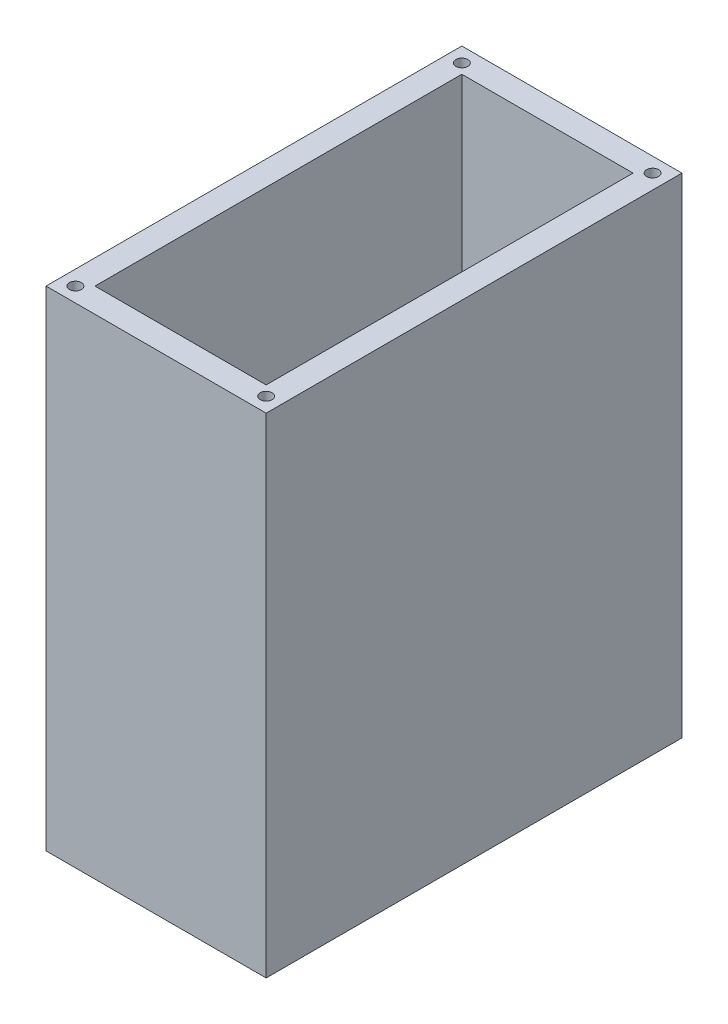
SolidWorks part; units mm, degrees
ref_plane "Front Plane" through (0, 0, 0) normal (0, 0, 1) x (1, 0, 0)
ref_plane "Top Plane" through (0, 0, 0) normal (0, 1, 0) x (1, 0, 0)
ref_plane "Right Plane" through (0, 0, 0) normal (1, 0, 0) x (0, 0, -1)
sketch "Sketch1" plane through (0, 0, 0) normal (0, 1, 0) x (1, 0, 0)
  line L1 (-22.5, 42.5) -> (22.5, 42.5)
  line L2 (-22.5, 42.5) -> (-22.5, -42.5)
  line L3 (-22.5, -42.5) -> (22.5, -42.5)
  line L4 (22.5, 42.5) -> (22.5, -42.5)
  line L5 (-22.5, 42.5) -> (22.5, -42.5) construction
  line L6 (-22.5, -42.5) -> (22.5, 42.5) construction
  point P0 (0, 0)
  dimension "D1" = 45
  dimension "D2" = 85
extrude "Boss-Extrude1" add sketch "Sketch1" along normal blind 100
shell "Shell1" thickness 5 removed face at (0, 100, 0)
sketch "Sketch2" plane through (0, 5, 0) normal (0, 1, 0) x (1, 0, 0)
  line L0 (-13.25, 0) -> (-13.25, -29)
  line L1 (-13.25, -29) -> (-1.25, -29)
  line L2 (-1.25, -29) -> (-1.25, -13.1909)
  line L3 (-16.25, 0) -> (-16.25, -32)
  line L4 (-16.25, -32) -> (1.75, -32)
  line L5 (1.75, -32) -> (1.75, -13.1339)
  line L6 (-13.25, 0) -> (-16.25, 0)
  line L7 (3.4294, 12.7985) -> (4.2058, 15.6963)
  line L8 (-4.2058, 15.6963) -> (-3.4294, 12.7985)
  line L9 (-1.25, -16.2019) -> (-1.25, -13.1909)
  line L10 (-1.25, -29) -> (-1.25, -12.0576) construction
  line L11 (1.75, -32) -> (1.75, -12.0576) construction
  line L12 (1.75, -16.1555) -> (1.75, -13.1339)
  line L13 (-1.25, -16.2019) -> (-1.25, -13.1909)
  line L14 (1.75, -13.1339) -> (1.75, -16.1555)
  line L19 (-1.25, -13.1909) -> (-1.25, -16.2019)
  line L20 (-13.25, -24) -> (-16.25, -24)
  line L21 (-16.25, -14) -> (-13.25, -14)
  circle A1 centre (0, 0) radius 16.25
  circle A2 centre (0, 0) radius 13.25
  arc A3 (1.75, -16.1555) -> (-1.25, -16.2019) centre (0, 0) cw
  arc A4 (1.75, -13.1339) -> (-1.25, -13.1909) centre (0, 0) cw
  dimension "D1" = 26.5
  dimension "D2" = 32.5
  dimension "D3" = 12
  dimension "D4" = 30
  dimension "D6" = 15
  dimension "D7" = 29
  dimension "D8" = 10
  dimension "D9" = 8
  dimension "D5" = 3
extrude "Boss-Extrude2" add sketch "Sketch2" along normal blind 15 contours A1 L2 L1 L0 L20 L3 L4 L5 | L21 L3 L20 L0 | A1 L3 L21 L0 | A2 L7 A1 L8 | L6 A1 L0 | A2 L2 A1 L5 region at (-14.994, 5, 9.8815) region at (-14.75, 5, 19) region at (-13.4898, 5, 26.5) region at (-14.46, 5, 3.5757) region at (0.2509, 5, 14.7221) region at (0, 5, -14.6324)
sketch "Sketch4" plane through (-13.25, 0, 0) normal (1, 0, 0) x (0, 0, -1)
  line L0 (0, 5) -> (-29, 5) construction
  line L1 (-29, 20) -> (-9, 20)
  line L2 (-29, 20) -> (-29, 17.5)
  line L3 (-29, 17.5) -> (-9, 17.5)
  line L4 (-9, 20) -> (-9, 17.5)
  dimension "D1" = 12.5
  dimension "D2" = 20
extrude "Boss-Extrude3" add sketch "Sketch4" along normal blind 1
sketch "Sketch5" plane through (-1.25, 0, 0) normal (-1, 0, 0) x (0, 0, 1)
  line L6 (29, 20) -> (29, 5) construction
  line L7 (13.1909, 20) -> (29, 20)
  line L8 (13.1909, 20) -> (13.1909, 18)
  line L9 (13.1909, 18) -> (29, 18)
  line L10 (29, 20) -> (29, 18)
  dimension "D1" = 2
extrude "Boss-Extrude4" add sketch "Sketch5" along normal blind 1
sketch "Sketch6" plane through (0, 0, 29) normal (0, 0, -1) x (-1, 0, 0)
  line L2 (12.25, 17.5) -> (2.25, 17.5)
  line L3 (12.25, 17.5) -> (12.25, 20)
  line L4 (12.25, 20) -> (2.25, 20)
  line L5 (2.25, 17.5) -> (2.25, 20)
extrude "Boss-Extrude5" add sketch "Sketch6" along normal blind 1
sketch "Sketch9" plane through (0, 20, 0) normal (0, 1, 0) x (1, 0, 0)
  line L1 (-5.0753, 17.3777) -> (5.4023, 17.3777)
  line L2 (-5.0753, 17.3777) -> (-5.0753, 11.055)
  line L3 (-5.0753, 11.055) -> (5.4023, 11.055)
  line L4 (5.4023, 17.3777) -> (5.4023, 11.055)
extrude "Cut-Extrude1" cut sketch "Sketch9" against normal blind 9
sketch "Sketch10" plane through (0, 100, 0) normal (0, 1, 0) x (1, 0, 0)
  line L0 (-22.5, 42.5) -> (-22.5, -42.5) construction
  line L1 (-22.5, -42.5) -> (22.5, -42.5) construction
  line L2 (22.5, -42.5) -> (22.5, 42.5) construction
  line L3 (22.5, 42.5) -> (-22.5, 42.5) construction
  circle A0 centre (-19.5, 39.5) radius 1.225
  circle A1 centre (19.5, 39.5) radius 1.225
  circle A2 centre (-19.5, -39.5) radius 1.225
  circle A3 centre (19.5, -39.5) radius 1.225
  dimension "D1" = 2.45
  dimension "D2" = 2.45
  dimension "D3" = 2.45
  dimension "D4" = 2.45
  dimension "D5" = 3
  dimension "D7" = 3
  dimension "D9" = 3
  dimension "D11" = 3
  dimension "D12" = 3
  dimension "D6" = 3
  dimension "D8" = 3
  dimension "D10" = 3
extrude "Cut-Extrude2" cut sketch "Sketch10" against normal blind 20
